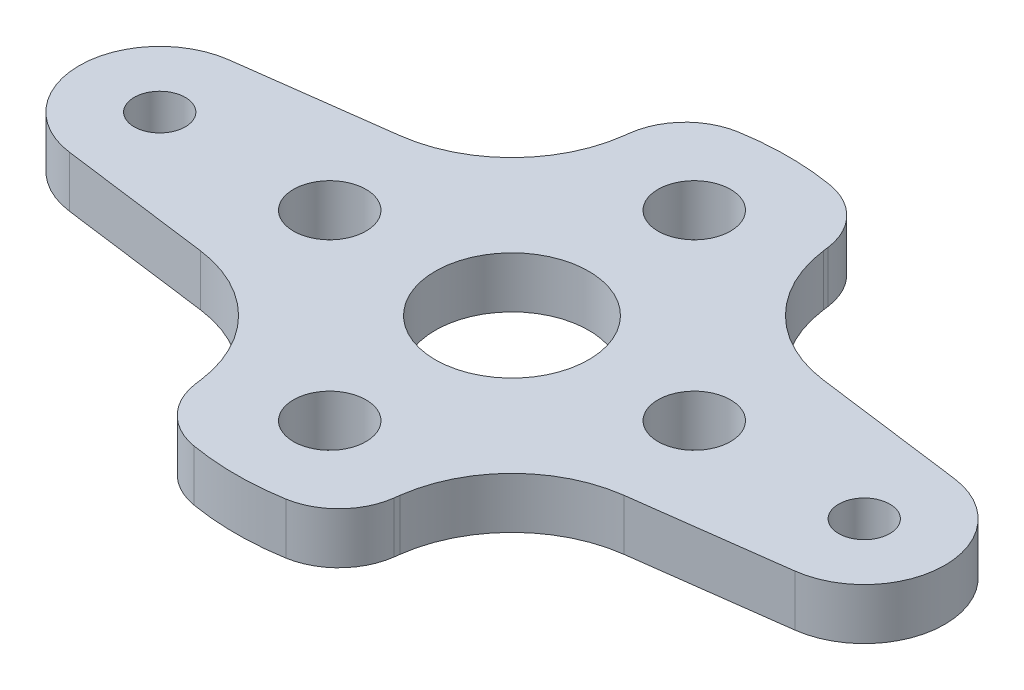
SolidWorks part; units mm, degrees
material "7075-T6, Plate (SS)"
ref_plane "Front Plane" through (0, 0, 0) normal (0, 0, 1) x (1, 0, 0)
ref_plane "Top Plane" through (0, 0, 0) normal (0, 1, 0) x (1, 0, 0)
ref_plane "Right Plane" through (0, 0, 0) normal (1, 0, 0) x (0, 0, -1)
sketch "Sketch1" plane through (0, 0, 0) normal (0, 1, 0) x (1, 0, 0)
  line L0 (0, 0) -> (0, 21.8652) construction
  line L1 (0, 0) -> (14.1869, 14.1869) construction
  line L2 (4.9572, 22.5178) -> (6.1926, 13.1344)
  line L3 (22.5178, -4.9572) -> (13.1344, -6.1926)
  line L4 (22.5178, 4.9572) -> (13.1344, 6.1926)
  line L5 (0, 0) -> (-14.1869, 14.1869) construction
  line L8 (-4.9572, 22.5178) -> (-6.1926, 13.1344)
  line L9 (-8.4853, 8.4853) -> (8.4853, -8.4853)
  arc A0 (-4.9572, 22.5178) -> (4.9572, 22.5178) centre (0, 21.8652) cw
  arc A1 (6.1926, 13.1344) -> (13.1344, 6.1926) centre (14.1869, 14.1869) ccw
  arc A2 (-6.1926, 13.1344) -> (-8.4853, 8.4853) centre (-14.1869, 14.1869) cw
  arc A3 (13.1344, -6.1926) -> (8.4853, -8.4853) centre (14.1869, -14.1869) ccw
  arc A4 (22.5178, -4.9572) -> (22.5178, 4.9572) centre (21.8652, 0) ccw
  point P18 (8.4853, 8.4853)
  dimension "D5" = 5
  dimension "D1" = 21.8652
  dimension "D2" = 45
  dimension "D3" = 12
  dimension "D4" = 7.5
extrude "Boss-Extrude1" add sketch "Sketch1" along normal blind 3.175
mirror "Mirror7" about plane through (-8.4853, 3.175, -8.4853) normal (0.7071, 0, -0.7071) of "Boss-Extrude1"
hole_wizard "1/8 (0.1250) Dowel Hole1" positions "Sketch2" profile "Sketch3" hole size "1/8" standard "ANSI Inch" end condition through all
sketch "Sketch2" plane through (0, 3.175, 0) normal (0, 1, 0) x (1, 0, 0)
  point P0 (0, 21.8652)
  point P3 (0, -21.8652)
  point P6 (-21.8652, 0)
  point P9 (21.8652, 0)
sketch "Sketch3" plane through (0, 3.175, -21.8652) normal (1, 0, 0) x (0, 0, 1)
  line L0 (0, 0) -> (0, 3.175)
  line L1 (0, 3.175) -> (1.5875, 3.175)
  line L2 (1.5875, 3.175) -> (1.5875, 0)
  line L5 (1.5875, 0) -> (0, 0)
  line L11 (0, -6.35) -> (0, 107.95) construction
  dimension "Thru Hole Dia." = 3.175
  dimension "Thru Hole Depth" = 3.175
sketch "Sketch4" plane through (0, 3.175, 0) normal (0, 1, 0) x (1, 0, 0)
  circle A0 centre (0, 0) radius 4.7625
  dimension "D1" = 9.525
extrude "Cut-Extrude1" cut sketch "Sketch4" against normal through all
hole_wizard "M4 Clearance Hole1" positions "Sketch5" profile "Sketch6" hole size "M4" standard "ANSI Metric" end condition through all
sketch "Sketch5" plane through (0, 3.175, 0) normal (0, 1, 0) x (1, 0, 0)
  line L0 (0, 0) -> (0, 11.3137) construction
  line L2 (0, 0) -> (11.3137, 0) construction
  circle A0 centre (0, 0) radius 11.3137 construction
  point P7 (0, 11.3137)
  point P12 (11.3137, 0)
  point P19 (0, -11.3137)
  point P21 (-11.3137, 0)
  dimension "D1" = 16
sketch "Sketch6" plane through (-11.3137, 3.175, 0) normal (1, 0, 0) x (0, 0, 1)
  line L0 (0, 0) -> (0, 3.175)
  line L1 (0, 3.175) -> (2.25, 3.175)
  line L2 (2.25, 3.175) -> (2.25, 0)
  line L5 (2.25, 0) -> (0, 0)
  line L11 (0, -6.35) -> (0, 107.95) construction
  dimension "Thru Hole Dia." = 4.5
  dimension "Thru Hole Depth" = 3.175
sketch "Sketch7" plane through (0, 3.175, 0) normal (0, 1, 0) x (1, 0, 0)
  line L8 (-4.9572, 22.5178) -> (-6.1926, 13.1344)
  line L9 (-13.1344, 6.1926) -> (-22.5178, 4.9572)
  line L10 (-22.5178, -4.9572) -> (-13.1344, -6.1926)
  line L11 (-6.1926, -13.1344) -> (-4.9572, -22.5178)
  line L12 (4.9572, -22.5178) -> (6.1926, -13.1344)
  line L13 (13.1344, -6.1926) -> (22.5178, -4.9572)
  line L14 (22.5178, 4.9572) -> (13.1344, 6.1926)
  line L15 (6.1926, 13.1344) -> (4.9572, 22.5178)
  line L16 (-5.8005, 16.1125) -> (-6.1926, 13.1344)
  line L17 (-13.1344, 6.1926) -> (-22.5178, 4.9572)
  line L18 (-22.5178, -4.9572) -> (-13.1344, -6.1926)
  line L19 (-6.1926, -13.1344) -> (-5.8005, -16.1125)
  line L20 (5.8005, -16.1125) -> (6.1926, -13.1344)
  line L21 (13.1344, -6.1926) -> (22.5178, -4.9572)
  line L22 (22.5178, 4.9572) -> (13.1344, 6.1926)
  line L23 (6.1926, 13.1344) -> (5.8005, 16.1125)
  arc A0 (5.8005, 16.1125) -> (-5.8005, 16.1125) centre (0, 0) ccw
  arc A1 (-5.8005, -16.1125) -> (5.8005, -16.1125) centre (0, 0) ccw
  arc A9 (4.9572, 22.5178) -> (-4.9572, 22.5178) centre (0, 21.8652) ccw
  arc A10 (-13.1344, 6.1926) -> (-6.1926, 13.1344) centre (-14.1869, 14.1869) ccw
  arc A11 (-22.5178, 4.9572) -> (-22.5178, -4.9572) centre (-21.8652, 0) ccw
  arc A12 (-6.1926, -13.1344) -> (-13.1344, -6.1926) centre (-14.1869, -14.1869) ccw
  arc A13 (-4.9572, -22.5178) -> (4.9572, -22.5178) centre (0, -21.8652) ccw
  arc A14 (13.1344, -6.1926) -> (6.1926, -13.1344) centre (14.1869, -14.1869) ccw
  arc A15 (22.5178, -4.9572) -> (22.5178, 4.9572) centre (21.8652, 0) ccw
  arc A16 (6.1926, 13.1344) -> (13.1344, 6.1926) centre (14.1869, 14.1869) ccw
  arc A18 (-13.1344, 6.1926) -> (-6.1926, 13.1344) centre (-14.1869, 14.1869) ccw
  arc A19 (-22.5178, 4.9572) -> (-22.5178, -4.9572) centre (-21.8652, 0) ccw
  arc A20 (-6.1926, -13.1344) -> (-13.1344, -6.1926) centre (-14.1869, -14.1869) ccw
  arc A22 (13.1344, -6.1926) -> (6.1926, -13.1344) centre (14.1869, -14.1869) ccw
  arc A23 (22.5178, -4.9572) -> (22.5178, 4.9572) centre (21.8652, 0) ccw
  arc A24 (6.1926, 13.1344) -> (13.1344, 6.1926) centre (14.1869, 14.1869) ccw
  circle M23 centre (0, 21.8652) radius 1.5875
  circle M24 centre (0, -21.8652) radius 1.5875
  arc M27 (4.9572, 22.5178) -> (-4.9572, 22.5178) centre (0, 21.8652) ccw
  line M28 (-4.9572, 22.5178) -> (-6.1926, 13.1344)
  line M34 (-6.1926, -13.1344) -> (-4.9572, -22.5178)
  arc M35 (-4.9572, -22.5178) -> (4.9572, -22.5178) centre (0, -21.8652) ccw
  line M36 (4.9572, -22.5178) -> (6.1926, -13.1344)
  line M42 (6.1926, 13.1344) -> (4.9572, 22.5178)
  dimension "D1" = 0
extrude "Cut-Extrude2" cut sketch "Sketch7" against normal through all contours A0 M42 M27 M28 M23 | A1 M34 M35 M36 M24 region at (0, 3.175, -26.707) region at (0, 3.175, 17.283)
fillet "Fillet1" radius 4 4 edges at (5.8005, 1.5875, -16.1125) (-5.8005, 1.5875, -16.1125) (-5.8005, 1.5875, 16.1125) (5.8005, 1.5875, 16.1125)
equation "\"0.25iin\"=10"
